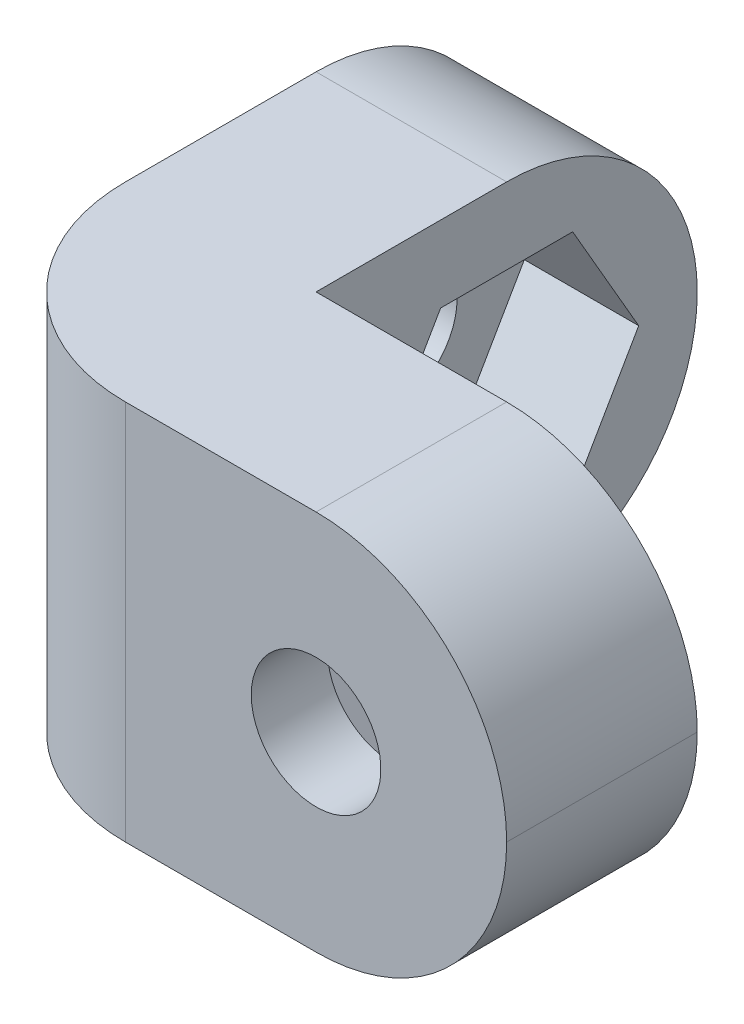
SolidWorks part; units mm, degrees
material "PEI"
ref_plane "Front Plane" through (0, 0, 0) normal (0, 0, 1) x (1, 0, 0)
ref_plane "Top Plane" through (0, 0, 0) normal (0, 1, 0) x (1, 0, 0)
ref_plane "Right Plane" through (0, 0, 0) normal (1, 0, 0) x (0, 0, -1)
sketch "Sketch1" plane through (0, 0, 0) normal (0, 1, 0) x (1, 0, 0)
  line L0 (0, 0) -> (0, 15)
  line L1 (0, 0) -> (15, 0)
  line L2 (15, 0) -> (15, 5)
  line L3 (15, 5) -> (5, 5)
  line L4 (5, 5) -> (5, 15)
  line L5 (5, 15) -> (0, 15)
  dimension "D1" = 5
  dimension "D2" = 15
extrude "Boss-Extrude1" add sketch "Sketch1" along normal blind 10
sketch "Sketch2" plane through (0, 0, -5) normal (0, 0, -1) x (-1, 0, 0)
  line L0 (-15, 10) -> (-15, 0) construction
  line L1 (-15, 0) -> (-5, 0) construction
  circle A0 centre (-10, 5) radius 1.7
  point P5 (-15, 5)
  point P9 (-10, 0)
  dimension "D1" = 3.4
extrude "Cut-Extrude1" cut sketch "Sketch2" against normal through all
sketch "Sketch3" plane through (5, 0, 0) normal (1, 0, 0) x (0, 0, -1)
  line L0 (15, 10) -> (15, 0) construction
  line L1 (5, 10) -> (15, 10) construction
  circle A0 centre (10, 5) radius 1.7
  point P5 (15, 5)
  point P9 (10, 10)
  dimension "D1" = 3.4
extrude "Cut-Extrude2" cut sketch "Sketch3" against normal through all
sketch "Sketch4" plane through (5, 0, 0) normal (1, 0, 0) x (0, 0, -1)
  line L1 (13.4641, 5) -> (11.7321, 8)
  line L2 (11.7321, 8) -> (8.2679, 8)
  line L3 (8.2679, 8) -> (6.5359, 5)
  line L4 (6.5359, 5) -> (8.2679, 2)
  line L5 (8.2679, 2) -> (11.7321, 2)
  line L6 (11.7321, 2) -> (13.4641, 5)
  circle A0 centre (10, 5) radius 3 construction
  dimension "D1" = 6
extrude "Cut-Extrude3" cut sketch "Sketch4" against normal blind 3
sketch "Sketch5" plane through (0, 0, -5) normal (0, 0, -1) x (-1, 0, 0)
  line L1 (-6.5359, 5) -> (-8.2679, 8)
  line L2 (-8.2679, 8) -> (-11.7321, 8)
  line L3 (-11.7321, 8) -> (-13.4641, 5)
  line L4 (-13.4641, 5) -> (-11.7321, 2)
  line L5 (-11.7321, 2) -> (-8.2679, 2)
  line L6 (-8.2679, 2) -> (-6.5359, 5)
  circle A0 centre (-10, 5) radius 3 construction
  dimension "D1" = 6
extrude "Cut-Extrude4" cut sketch "Sketch5" against normal blind 3
fillet "Fillet1" radius 5 5 edges at (0, 5, 0) (15, 10, -2.5) (15, 0, -2.5) (2.5, 0, -15) (2.5, 10, -15)
